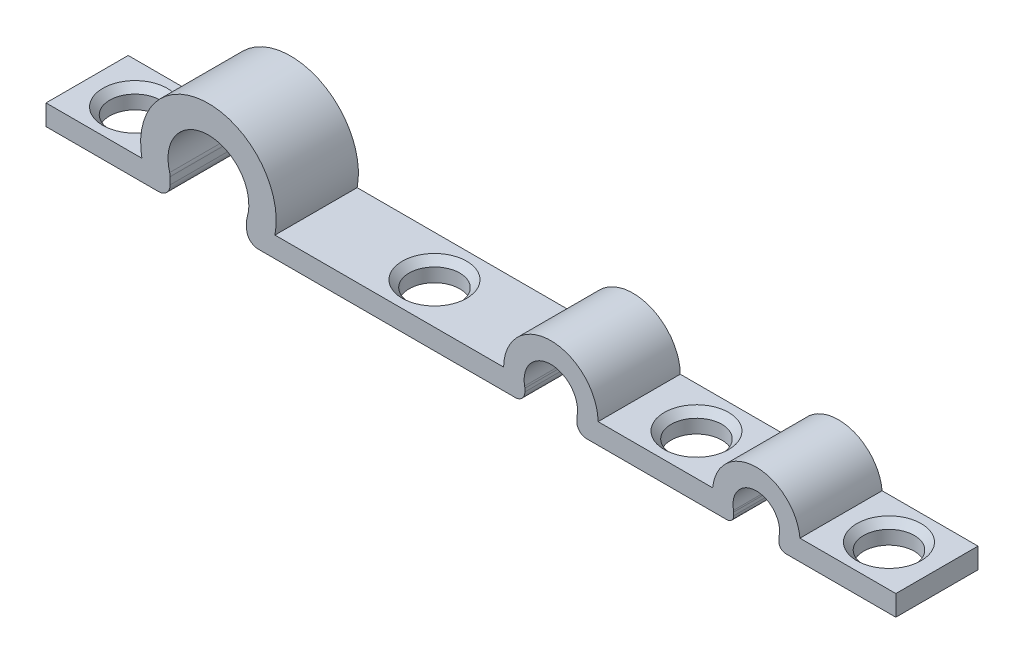
SolidWorks part; units mm, degrees
ref_plane "Front Plane" through (0, 0, 0) normal (0, 0, 1) x (1, 0, 0)
ref_plane "Top Plane" through (0, 0, 0) normal (0, 1, 0) x (1, 0, 0)
ref_plane "Right Plane" through (0, 0, 0) normal (1, 0, 0) x (0, 0, -1)
sketch "Sketch1" plane through (0, 0, 0) normal (0, 0, 1) x (1, 0, 0)
  line L0 (-31.0219, 0) -> (-22.8068, 0)
  line L1 (-31.0219, 0) -> (-31.0219, 1.5)
  line L2 (-31.0219, 1.5) -> (-24.0219, 1.5)
  line L3 (-14.306, 1.5) -> (2.3864, 1.5)
  line L4 (9.2857, 1.5) -> (17.6501, 1.5)
  line L5 (24.0219, 1.5) -> (31.0219, 1.5)
  line L6 (31.0219, 1.5) -> (31.0219, 0)
  line L7 (-15.5211, 0) -> (3.236, 0)
  line L8 (8.436, 0) -> (18.686, 0)
  line L9 (22.986, 0) -> (31.0219, 0)
  line L10 (-21.9568, 1.3685) -> (-21.9568, 0.85)
  line L11 (-16.3711, 0.85) -> (-16.3711, 1.3685)
  line L12 (3.936, 0.9377) -> (3.936, 0.7)
  line L13 (7.736, 0.9377) -> (7.736, 0.7)
  line L14 (19.186, 0.5) -> (19.186, 0.7336)
  line L15 (22.486, 0.5) -> (22.486, 0.7336)
  line L16 (-31.0219, 0) -> (31.0219, 0) construction
  arc A0 (-16.336, 1.6104) -> (-21.992, 1.6104) centre (-19.164, 2.45) ccw
  arc A1 (7.7492, 1.073) -> (3.9228, 1.073) centre (5.836, 1.45) ccw
  arc A2 (22.4974, 0.8396) -> (19.1747, 0.8396) centre (20.836, 1.2) ccw
  arc A3 (-14.306, 1.5) -> (-24.0219, 1.5) centre (-19.164, 2.45) ccw
  arc A4 (9.2857, 1.5) -> (2.3864, 1.5) centre (5.836, 1.45) ccw
  arc A5 (24.0219, 1.5) -> (17.6501, 1.5) centre (20.836, 1.2) ccw
  arc A6 (-16.3711, 1.3685) -> (-16.336, 1.6104) centre (-15.5211, 1.3685) cw
  arc A7 (-21.9568, 1.3685) -> (-21.992, 1.6104) centre (-22.8068, 1.3685) ccw
  arc A8 (-15.5211, 0) -> (-16.3711, 0.85) centre (-15.5211, 0.85) cw
  arc A9 (-22.8068, 0) -> (-21.9568, 0.85) centre (-22.8068, 0.85) ccw
  arc A10 (8.436, 0) -> (7.736, 0.7) centre (8.436, 0.7) cw
  arc A11 (7.736, 0.9377) -> (7.7492, 1.073) centre (8.436, 0.9377) cw
  arc A12 (3.936, 0.9377) -> (3.9228, 1.073) centre (3.236, 0.9377) ccw
  arc A13 (3.936, 0.7) -> (3.236, 0) centre (3.236, 0.7) cw
  arc A14 (22.986, 0) -> (22.486, 0.5) centre (22.986, 0.5) cw
  arc A15 (22.486, 0.7336) -> (22.4974, 0.8396) centre (22.986, 0.7336) cw
  arc A16 (19.186, 0.7336) -> (19.1747, 0.8396) centre (18.686, 0.7336) ccw
  arc A17 (19.186, 0.5) -> (18.686, 0) centre (18.686, 0.5) cw
  point P26 (-21.9568, 1.5)
  point P51 (0, 0)
  dimension "D1" = 5.9
  dimension "D2" = 3.9
  dimension "D3" = 3.4
  dimension "D4" = 25
  dimension "D5" = 15
  dimension "D6" = 0.5
  dimension "D7" = 0.5
  dimension "D8" = 0.5
  dimension "D10" = 2
  dimension "D11" = 1.5
  dimension "D12" = 1.5
  dimension "D15" = 0.85
  dimension "D17" = 0.7
  dimension "D19" = 0.5
  dimension "D9" = 1.5
  dimension "D13" = 7
  dimension "D14" = 7
  dimension "D16" = 1.9
  dimension "D18" = 1.65
extrude "Boss-Extrude1" add sketch "Sketch1" along normal mid plane 6
sketch "Sketch2" plane through (0, 0, 0) normal (0, 1, 0) x (1, 0, 0)
  line L0 (-24.0219, -3) -> (-31.0219, -3) construction
  line L1 (-24.0219, -3) -> (-31.0219, -3) construction
  line L2 (17.6501, -3) -> (9.2857, -3) construction
  line L3 (17.6501, -3) -> (9.2857, -3) construction
  line L4 (31.0219, -3) -> (24.0219, -3) construction
  line L5 (31.0219, -3) -> (24.0219, -3) construction
  line L6 (2.3864, -3) -> (-14.306, -3) construction
  line L7 (2.3864, -3) -> (-14.306, -3) construction
  circle A0 centre (-27.5219, 0) radius 1.85
  circle A1 centre (-5.6598, 0) radius 1.85
  circle A4 centre (27.5219, 0) radius 1.85
  circle A5 centre (13.4679, 0) radius 1.85
  point P10 (-5.9598, -3)
  point P15 (-27.5219, -3)
  point P19 (13.4679, -3)
  point P22 (27.5219, -3)
  dimension "D1" = 3.7
  dimension "D2" = 0.3
extrude "Cut-Extrude2" cut sketch "Sketch2" along normal up to next contours A0 | A1 | A5 | A4 region at (-27.5219, 0, 0) region at (-5.6598, 0, 0) region at (27.5219, 0, 0) region at (13.4679, 0, 0)
chamfer "Chamfer2" distance 0.5 angle 45 4 edges at (29.3719, 1.5, 0) (15.3179, 1.5, 0) (-3.8098, 1.5, 0) (-25.6719, 1.5, 0)
